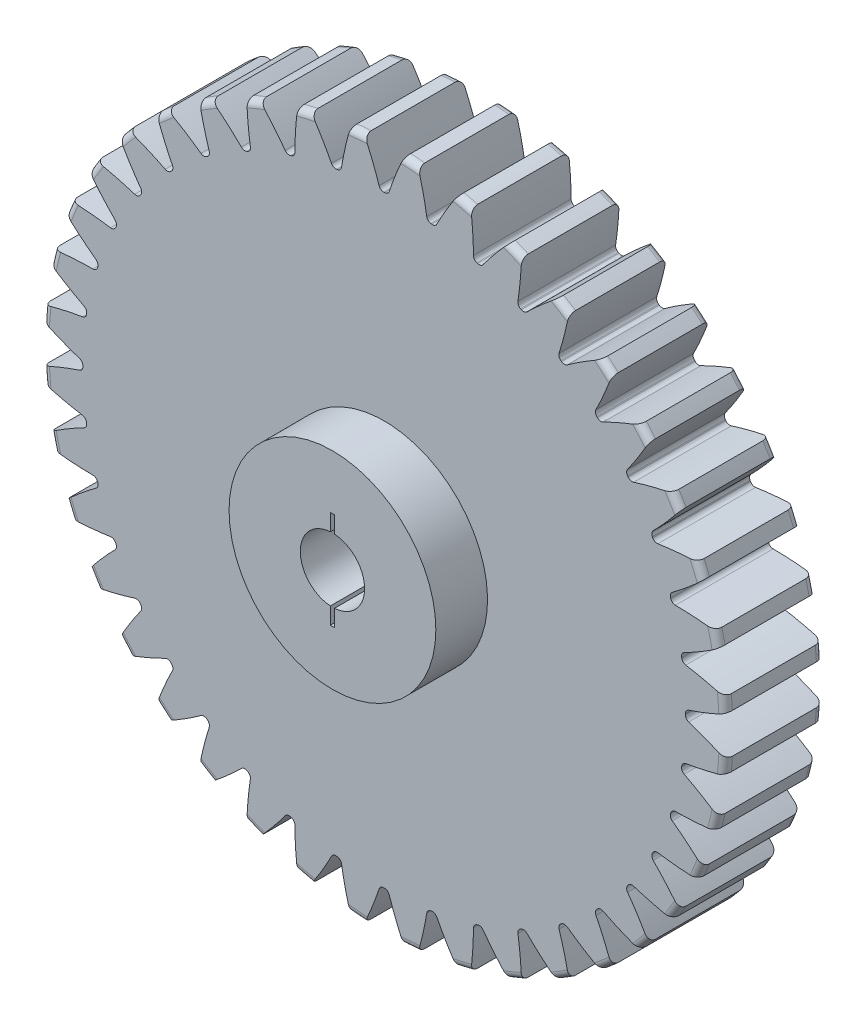
SolidWorks part; units mm, degrees
ref_plane "Front Plane" through (0, 0, 0) normal (0, 0, 1) x (1, 0, 0)
ref_plane "Top Plane" through (0, 0, 0) normal (0, 1, 0) x (1, 0, 0)
ref_plane "Right Plane" through (0, 0, 0) normal (1, 0, 0) x (0, 0, -1)
sketch "Sketch1" plane through (0, 0, 0) normal (0, 0, 1) x (1, 0, 0)
  line L0 (-508, 0) -> (508, 0) construction
  circle A0 centre (0, 0) radius 21 construction
  circle A1 centre (0, 0) radius 20 construction
  circle A2 centre (0, 0) radius 18.5 construction
  circle A3 centre (0, 0) radius 8 construction
  circle A4 centre (0, 0) radius 4 construction
  dimension "D2" = 1
  dimension "D3" = 2.5
  dimension "D1" = 2.5
sketch "Sketch2" plane through (0, 0, 0) normal (1, 0, 0) x (0, 0, -1)
  line L0 (0, 0) -> (-6, 0) construction
  line L1 (-6, 0) -> (-12, 0) construction
  dimension "Overall Width" = 12
  dimension "Face Width" = 6
sketch "Sketch4" plane through (0, 0, 0) normal (1, 0, 0) x (0, 0, -1)
  line L0 (-12, 4) -> (-12, 8)
  line L1 (-12, 8) -> (-6, 8)
  line L2 (-6, 8) -> (-6, 21)
  line L3 (-6, 21) -> (0, 21)
  line L4 (0, 21) -> (0, 4)
  line L5 (-6, 8) -> (-6, 0) construction
  line L6 (0, 21) -> (0, -21) construction
  line L7 (-6, 8) -> (0, 8) construction
  line L12 (-12, 4) -> (0, 4)
revolve "Revolve1" add sketch "Sketch4" angle 360 about L1
fillet "Fillet2" radius 0.42 4 edges at (0, 8, 12) (0, 8, 6) (0, 21, 6) (0, 21, 0)
sketch "Sketch7" plane through (0, 0, 6) normal (0, 0, 1) x (1, 0, 0)
  line L0 (0, 0) -> (0, 21) construction
  line L1 (0.7852, 19.9846) -> (1.1869, 20.9664) construction
  line L3 (1.6476, 20.9353) -> (1.5692, 19.9383) construction
  line L4 (1.5692, 19.9383) -> (1.4515, 18.443) construction
  line L5 (0, 0) -> (1.4515, 18.443) construction
  line L6 (0.7852, 19.9846) -> (0, 0) construction
  line L7 (0.7852, 19.9846) -> (0.8245, 20.9838) construction
  line L8 (0.7852, 19.9846) -> (0, 0) construction
  circle A0 centre (0, 0) radius 21 construction
  arc A1 (-0.027, 18.5) -> (0.027, 18.5) centre (0, 0) cw
  circle A2 centre (0, 0) radius 18.5 construction
  arc A3 (-0.7852, 19.9846) -> (0.7852, 19.9846) centre (0, 0) cw construction
  circle A4 centre (0, 0) radius 20 construction
  arc A5 (2.0774, 20.897) -> (1.2172, 20.9647) centre (0, 0) ccw construction
  arc A6 (0.7852, 19.9846) -> (2.3507, 19.8614) centre (0, 0) cw construction
  arc A7 (-1.2172, 20.9647) -> (1.2172, 20.9647) centre (0, 0) cw
  arc A8 (0.3122, 18.7056) -> (1.2172, 20.9647) centre (19.296, 12.4116) cw
  arc A9 (-0.3122, 18.7056) -> (-1.2172, 20.9647) centre (-19.296, 12.4116) ccw
  arc A10 (-0.027, 18.5) -> (-0.3122, 18.7056) centre (-0.0274, 18.8) cw
  arc A11 (0.027, 18.5) -> (0.3122, 18.7056) centre (0.0274, 18.8) ccw
  point P26 (-0.2447, 18.4984)
  point P29 (0.2447, 18.4984)
  dimension "D4" = 0.3
  dimension "D5" = 20
  dimension "D3" = 20
  dimension "D1" = 3.1416
  dimension "D2" = 1.5708
extrude "Cut-Extrude2" cut sketch "Sketch7" against normal through all
pattern_circular "CirPattern1" count 40 over 360 about axis through (0, 0, 12) along (0, 0, -1) of "Cut-Extrude2"
sketch "Sketch8" plane through (0, 0, 0) normal (0, 0, -1) x (-1, 0, 0)
  circle A0 centre (0, 0) radius 2
  circle A1 centre (0, 0) radius 4
  circle A2 centre (0, 0) radius 4 construction
  dimension "D1" = 4
extrude "Boss-Extrude1" add sketch "Sketch8" against normal up to surface (12 mm away) up to face at (0, -7.58, 12)
sketch "Sketch9" plane through (0, 0, 12) normal (0, 0, 1) x (1, 0, 0)
  circle A0 centre (0, 0) radius 8.42
  dimension "D1" = 16.84
extrude "Cut-Extrude3" cut sketch "Sketch9" against normal up to surface (6 mm away) up to face at (0, 0, 6)
ref_plane "Plane1" through (0, 0, 3) normal (0, 0, 1) x (1, 0, 0)
sketch "Sketch10" plane through (0, 0, 3) normal (0, 0, 1) x (1, 0, 0)
  circle A0 centre (0, 0) radius 1.975
  circle A1 centre (0, 0) radius 6.35
  dimension "D1" = 3.95
  dimension "D2" = 12.7
extrude "Boss-Extrude2" add sketch "Sketch10" along normal mid plane 12.35
sketch "Sketch12" plane through (0, 0, 9.175) normal (0, 0, 1) x (1, 0, 0)
  line L0 (-0.127, 0) -> (0.127, 0) construction
  line L1 (0.127, 3) -> (0.127, -3)
  line L2 (0.127, 3) -> (-0.127, 3)
  line L3 (-0.127, 3) -> (-0.127, -3)
  line L4 (-0.127, -3) -> (0.127, -3)
  point P4 (0.127, 0)
  point P5 (0, 0)
  dimension "D1" = 0.254
  dimension "D2" = 6
extrude "Cut-Extrude4" cut sketch "Sketch12" against normal through all
equation "\"D1@Sketch1\"=2.5*(\"Pitch Dia.@Sketch1\"/\"Number of Teeth@Sketch1\")"
equation "\"D1@CirPattern1\"=\"Number of Teeth@Sketch1\""
equation "\"D1@Fillet2\"=\"OD@Sketch1\"*.01"
equation "\"D1@Sketch7\"=3.14159*(\"Pitch Dia.@Sketch1\"/\"Number of Teeth@Sketch1\")"
equation "\"D2@Sketch7\"=\"D1@Sketch7\"/2"
equation "\"D4@Sketch7\"=\"D1@Sketch7\"*.0955"
equation "\"D5@Sketch7\"=\"Pitch Dia.@Sketch1\"/2"
